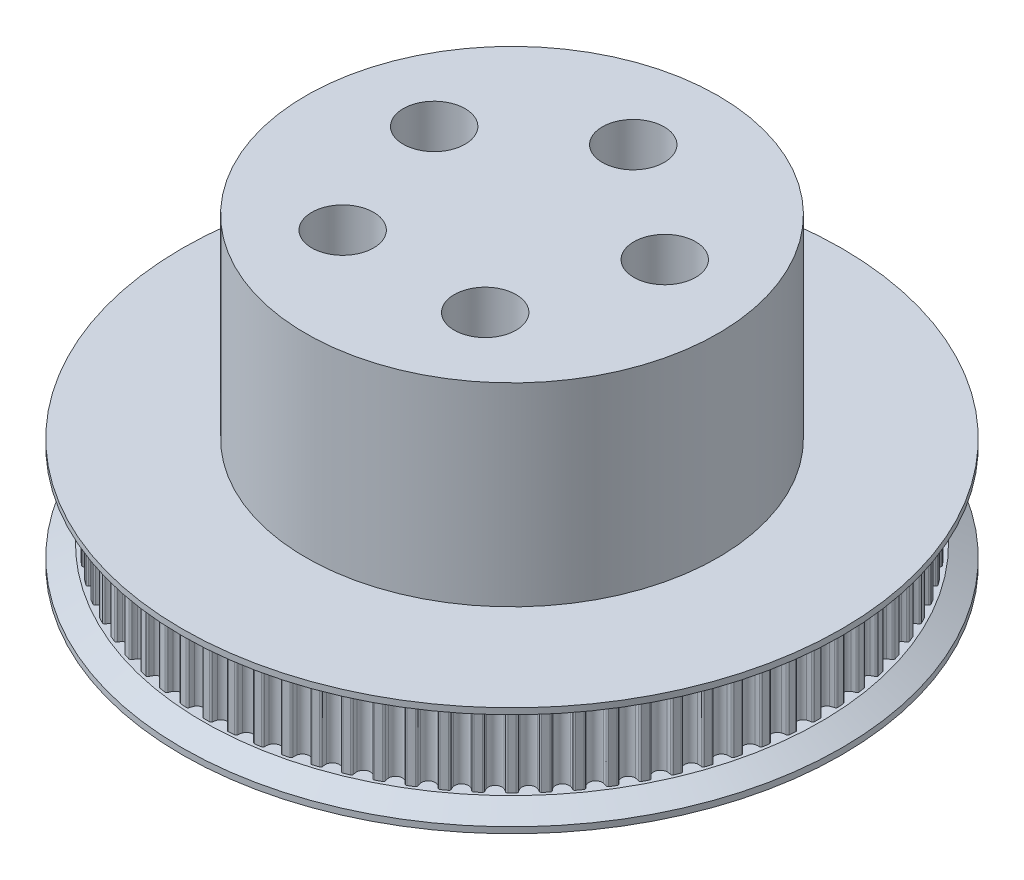
SolidWorks part; units mm, degrees
ref_plane "Front" through (0, 0, 0) normal (0, 0, 1) x (1, 0, 0)
ref_plane "Top" through (0, 0, 0) normal (0, 1, 0) x (1, 0, 0)
ref_plane "Right" through (0, 0, 0) normal (1, 0, 0) x (0, 0, -1)
sketch "Sketch1" plane through (0, 0, 0) normal (0, 1, 0) x (1, 0, 0)
  line L0 (0, 0) -> (0, 25.4648) construction
  line L1 (0, 25.2108) -> (0, 25.8408)
  line L2 (0, 0) -> (0.9997, 25.4452) construction
  line L3 (1.978, 25.1331) -> (2.0274, 25.7611)
  line L4 (1.3894, 25.1757) -> (1.4033, 25.4261) construction
  arc A0 (0.2468, 25.2096) -> (0.3946, 25.0747) centre (0.2453, 25.0596) cw
  arc A1 (0.3946, 25.0747) -> (0.4741, 24.773) centre (1.3894, 25.1757) ccw
  circle A2 centre (0, 0) radius 25.4648 construction
  arc A3 (0.2468, 25.2096) -> (0, 25.2108) centre (0, 0) ccw
  arc A4 (0.9603, 24.4419) -> (0, 24.4608) centre (0, 0) ccw construction
  arc A5 (0.4741, 24.773) -> (1.471, 24.7339) centre (0.9821, 24.9965) ccw
  arc A6 (1.3894, 25.1757) -> (0.9899, 25.1946) centre (0, 0) ccw construction
  arc A7 (0, 25.8408) -> (2.0274, 25.7611) centre (0, 0) cw
  arc A8 (1.574, 25.0284) -> (1.471, 24.7339) centre (0.5901, 25.2071) cw
  arc A9 (1.7319, 25.1512) -> (1.574, 25.0284) centre (1.7216, 25.0016) ccw
  arc A10 (1.7319, 25.1512) -> (1.978, 25.1331) centre (0, 0) cw
  dimension "D1" = 0.15
  dimension "D4" = 50.9296
  dimension "D5" = 1
  dimension "D7" = 0.555
  dimension "D3" = 2.25
  dimension "D8" = 0.75
  dimension "D6" = 0.254
  dimension "D2" = 0.4
  dimension "D9" = 1.38
  dimension "D11" = 0.404
  dimension "D12" = 0.2508
  dimension "D10" = 0.909
sketch "Sketch2" plane through (0, 0, 0) normal (0, 1, 0) x (1, 0, 0)
  circle A0 centre (0, 0) radius 25.4648 construction
  circle A1 centre (0, 0) radius 25.4648
  circle A2 centre (0, 0) radius 6
  dimension "D1" = 12
extrude "Boss-Extrude1" add sketch "Sketch2" along normal mid plane 6
sketch "Sketch6" plane through (0, 0, 0) normal (0, 1, 0) x (1, 0, 0)
  line L0 (0, 25.2008) -> (0, 25.8408)
  line L1 (1.9772, 25.1231) -> (2.0274, 25.7611)
  arc A7 (2.0274, 25.7611) -> (0, 25.8408) centre (0, 0) ccw construction
  arc A8 (2.0274, 25.7611) -> (0, 25.8408) centre (0, 0) ccw
  arc A14 (1.7312, 25.1413) -> (1.5838, 25.0266) centre (1.7216, 25.0016) ccw
  arc A15 (1.4798, 24.7291) -> (1.5838, 25.0266) centre (0.5901, 25.2071) ccw
  arc A16 (0.4649, 24.769) -> (1.4798, 24.7291) centre (0.9821, 24.9965) ccw
  arc A17 (0.3846, 25.0737) -> (0.4649, 24.769) centre (1.3894, 25.1757) ccw
  arc A18 (0.3846, 25.0737) -> (0.2467, 25.1996) centre (0.2453, 25.0596) ccw
  arc A19 (0.2467, 25.1996) -> (0, 25.2008) centre (0, 0) ccw
  arc A20 (1.9772, 25.1231) -> (1.7312, 25.1413) centre (0, 0) ccw
  arc A21 (1.7312, 25.1413) -> (1.5838, 25.0266) centre (1.7216, 25.0016) ccw
  arc A22 (1.4798, 24.7291) -> (1.5838, 25.0266) centre (0.5901, 25.2071) ccw
  arc A23 (0.4649, 24.769) -> (1.4798, 24.7291) centre (0.9821, 24.9965) ccw
  arc A24 (0.3846, 25.0737) -> (0.4649, 24.769) centre (1.3894, 25.1757) ccw
  arc A25 (0.3846, 25.0737) -> (0.2467, 25.1996) centre (0.2453, 25.0596) ccw
  arc A26 (0.2467, 25.1996) -> (0, 25.2008) centre (0, 0) ccw
  arc A27 (1.9772, 25.1231) -> (1.7312, 25.1413) centre (0, 0) ccw
extrude "Cut-Extrude3" cut sketch "Sketch6" against normal through all both and the other way through all
pattern_circular "CirPattern3" count 80 over 360 about axis through (0, 3, 0) along (0, -1, 0) of "Cut-Extrude3"
sketch "Sketch3" plane through (0, 0, 0) normal (0, 0, 1) x (1, 0, 0)
  line L0 (0, 0) -> (0, 9.5108) construction
  line L1 (-25.4648, 3) -> (-27.1968, 4)
  line L2 (-27.1968, 4) -> (-27.1968, 4.5)
  line L3 (-27.1968, 4.5) -> (-6, 4.5)
  line L4 (-6, 4.5) -> (-6, 3)
  line L5 (-6, 3) -> (-25.4648, 3)
  line L6 (6, 3) -> (-6, 3) construction
  dimension "D4" = 50.9296
  dimension "D1" = 1.5
  dimension "D2" = 0.5
  dimension "D3" = 30
revolve "Revolve1" add sketch "Sketch3" angle 360 about L0
mirror "Mirror1" about plane through (0, 0, 0) normal (0, 1, 0) of "Revolve1"
sketch "Sketch4" plane through (0, 0, 0) normal (0, 0, 1) x (1, 0, 0)
  line L0 (0, 0) -> (0, 14.0175) construction
  line L1 (27.1968, 4.5) -> (-27.1968, 4.5) construction
  line L2 (-6, 4.5) -> (-12.5, 4.5)
  line L3 (-6, 4.5) -> (-6, 10.5)
  line L4 (-6, 10.5) -> (-12.5, 10.5)
  line L5 (-12.5, 4.5) -> (-12.5, 10.5)
  dimension "D2" = 6
  dimension "D1" = 6.5
revolve "Revolve2" add sketch "Sketch4" angle 360 about L0
sketch "Sketch5" plane through (0, 0, 0) normal (0, 0, 1) x (1, 0, 0)
  line L1 (0, 4.5) -> (0, 10.5) construction
  line L2 (12.5, 10.5) -> (-12.5, 10.5) construction
  line L7 (-12.5, 10.5) -> (-12.5, 4.5) construction
  line L8 (-12.5, 10.5) -> (-12.5, 4.5) construction
  circle A0 centre (0, 7.5) radius 1.6
  dimension "D1" = 3.2
extrude "Cut-Extrude2" cut sketch "Sketch5" along normal through all
pattern_circular "CirPattern2" count 2 over 90 about axis through (0, 3, 0) along (0, -1, 0) of "Cut-Extrude2" reverse direction yes
sketch "Esboço1" plane through (0, -4.5, 0) normal (0, -1, 0) x (1, 0, 0)
  circle A0 centre (0, 0) radius 17
  dimension "D1" = 34
extrude "Ressalto-extrusão1" add sketch "Esboço1" against normal blind 25
sketch "Esboço2" plane through (0, -4.5, 0) normal (0, -1, 0) x (1, 0, 0)
  circle A0 centre (0, -10) radius 2.55
  circle A1 centre (-9.5106, -3.0902) radius 2.55
  circle A2 centre (-5.8779, 8.0902) radius 2.55
  circle A3 centre (5.8779, 8.0902) radius 2.55
  circle A4 centre (9.5106, -3.0902) radius 2.55
  point P13 (0, 0)
  dimension "D1" = 5.1
  dimension "D2" = 10
  dimension "D3" = 5
extrude "Corte-extrusão1" cut sketch "Esboço2" against normal up to surface (25 mm away) up to face at (0, 20.5, -17)
equation "\"belt-step\"= 2"
equation "\"pulley-teeth\"= 80"
equation "\"pulley-dia\"= ( \"belt-step\" * \"pulley-teeth\" ) / Pi"
equation "\"D3@Sketch1\"=(360/\"pulley-teeth\")/2"
equation "\"D4@Sketch1\"=\"pulley-dia\""
equation "\"bore-dia\"= 12"
equation "\"belt-thick\"= 6"
equation "\"D4@Sketch3\"=\"pulley-dia\""
equation "\"D1@Sketch2\"=\"bore-dia\""
equation "\"D1@Boss-Extrude1\"=\"belt-thick\""
equation "\"teeth-offset\"= 0.01"
equation "\"D1@Sketch6\"=\"teeth-offset\""
equation "\"D1@CirPattern3\"=\"pulley-teeth\""
equation "\"flange-wall\"= 6.5"
equation "\"D1@Sketch4\"=\"flange-wall\""
equation "\"flange-h\"= 6"
equation "\"screw-dia\"= 3.2"
equation "\"D2@Sketch4\"=\"flange-h\""
equation "\"D1@Sketch5\"=\"screw-dia\""
equation "\"D10@Sketch1\"=(0.4/(Pi*(\"pulley-dia\"-(2*\"D12@Sketch1\"))))*360"
